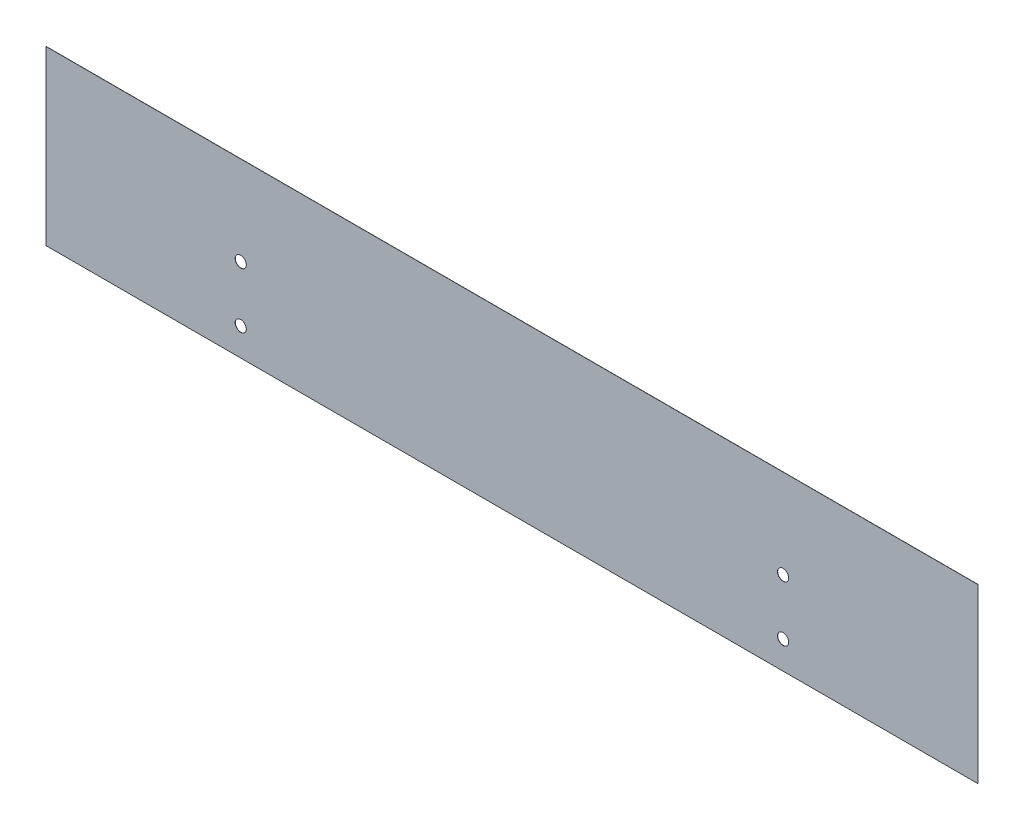
SolidWorks part; units mm, degrees
ref_plane "Front Plane" through (0, 0, 0) normal (0, 0, 1) x (1, 0, 0)
ref_plane "Top Plane" through (0, 0, 0) normal (0, 1, 0) x (1, 0, 0)
ref_plane "Right Plane" through (0, 0, 0) normal (1, 0, 0) x (0, 0, -1)
sketch "Sketch1" plane through (0, 0, 0) normal (0, 0, 1) x (1, 0, 0)
  line L1 (-167.5, -31) -> (167.5, -31)
  line L2 (-167.5, -31) -> (-167.5, 31)
  line L3 (-167.5, 31) -> (167.5, 31)
  line L4 (167.5, -31) -> (167.5, 31)
  line L5 (-167.5, -31) -> (167.5, 31) construction
  line L6 (-167.5, 31) -> (167.5, -31) construction
  point P0 (0, 0)
  dimension "D1" = 335
  dimension "D2" = 62
extrude "Body" add sketch "Sketch1" along normal blind 0.0625
sketch "Sketch2" plane through (0, 0, 0.0625) normal (0, 0, 1) x (1, 0, 0)
  line L0 (-61.5, -1) -> (61.5, -1) construction
  line L1 (61.5, -1) -> (61.5, -21) construction
  line L2 (61.5, -21) -> (-61.5, -21) construction
  line L3 (-61.5, -21) -> (-61.5, -1) construction
  line L4 (0, -1) -> (0, -21) construction
  line L5 (-167.5, -31) -> (167.5, -31) construction
  circle A0 centre (-61.5, -1) radius 2
  circle A1 centre (-61.5, -21) radius 2
  circle A2 centre (61.5, -1) radius 2
  circle A3 centre (61.5, -21) radius 2
  dimension "D4" = 4
  dimension "D1" = 123
  dimension "D2" = 20
  dimension "D3" = 10
extrude "Camera Mounting holes" [suppressed] cut sketch "Sketch2" against normal blind 0.0625
sketch "Sketch3" plane through (0, 0, 0.0625) normal (0, 0, 1) x (1, 0, 0)
  line L0 (-97.5, -1) -> (97.5, -1) construction
  line L1 (-97.5, -21) -> (97.5, -21) construction
  line L2 (-97.5, -1) -> (-97.5, -21) construction
  line L3 (97.5, -1) -> (97.5, -21) construction
  line L4 (-167.5, -31) -> (167.5, -31) construction
  line L5 (-167.5, 31) -> (-167.5, -31) construction
  line L6 (167.5, -31) -> (167.5, 31) construction
  circle A0 centre (-97.5, -1) radius 2
  circle A1 centre (-97.5, -21) radius 2
  circle A2 centre (97.5, -1) radius 2
  circle A3 centre (97.5, -21) radius 2
  dimension "D1" = 4
  dimension "D2" = 10
  dimension "D3" = 20
  dimension "D4" = 70
  dimension "D5" = 70
extrude "Mounting Holes" cut sketch "Sketch3" against normal blind 0.0625
sketch "Sketch4" plane through (0, 0, 0.0625) normal (0, 0, 1) x (1, 0, 0)
  line L0 (-167.5, -31) -> (167.5, -31) construction
  line L1 (-78.4073, -21) -> (-29.4073, -21)
  line L2 (-78.4073, -21) -> (-78.4073, 19)
  line L3 (-78.4073, 19) -> (-29.4073, 19)
  line L4 (-29.4073, -21) -> (-29.4073, 19)
  line L5 (-53.9073, 19) -> (-53.9073, -21) construction
  line L6 (167.5, 31) -> (-167.5, 31) construction
  line L7 (74.5329, 16) -> (94.5329, 16)
  line L8 (74.5329, 16) -> (74.5329, 31)
  line L9 (74.5329, 31) -> (94.5329, 31)
  line L10 (94.5329, 16) -> (94.5329, 31)
  dimension "D1" = 40
  dimension "D2" = 10
  dimension "D3" = 49
  dimension "D4" = 15
  dimension "D5" = 20
